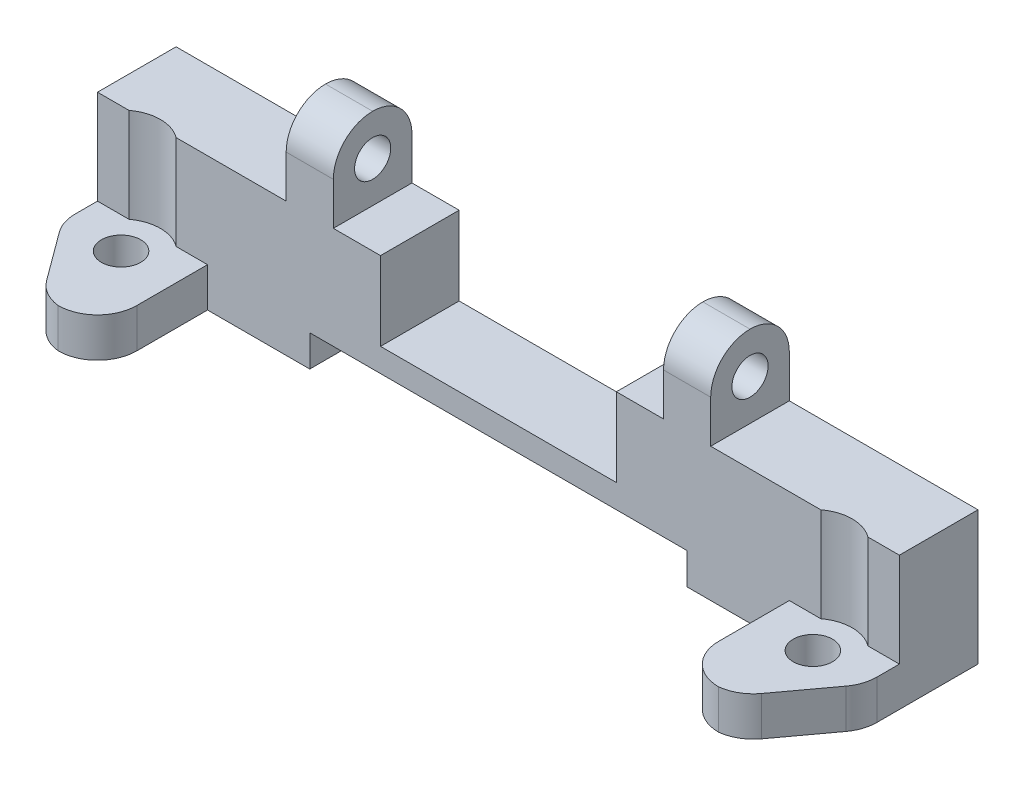
SolidWorks part; units mm, degrees
material "Sculpteo SLS"
ref_plane "Front Plane" through (0, 0, 0) normal (0, 0, 1) x (1, 0, 0)
ref_plane "Top Plane" through (0, 0, 0) normal (0, 1, 0) x (1, 0, 0)
ref_plane "Right Plane" through (0, 0, 0) normal (1, 0, 0) x (0, 0, -1)
sketch "Sketch1" plane through (0, 0, 0) normal (0, 1, 0) x (1, 0, 0)
  line L1 (25.5, -2.5) -> (-25.5, -2.5)
  line L2 (25.5, -2.5) -> (25.5, 2.5)
  line L3 (25.5, 2.5) -> (-25.5, 2.5)
  line L4 (-25.5, -2.5) -> (-25.5, 2.5)
  line L5 (25.5, -2.5) -> (-25.5, 2.5) construction
  line L6 (25.5, 2.5) -> (-25.5, -2.5) construction
  point P0 (0, 0)
  dimension "D1" = 51
  dimension "D2" = 5
extrude "Boss-Extrude1" add sketch "Sketch1" along normal blind 8.5
sketch "Sketch2" plane through (0, 8.5, 0) normal (0, 1, 0) x (1, 0, 0)
  line L0 (25.5, 2.5) -> (-25.5, 2.5) construction
  line L1 (7.5, -2.5) -> (-7.5, -2.5)
  line L2 (7.5, -2.5) -> (7.5, 2.5)
  line L3 (7.5, 2.5) -> (-7.5, 2.5)
  line L4 (-7.5, -2.5) -> (-7.5, 2.5)
  line L5 (7.5, -2.5) -> (-7.5, 2.5) construction
  line L6 (7.5, 2.5) -> (-7.5, -2.5) construction
  point P0 (0, 0)
  dimension "D1" = 15
extrude "Cut-Extrude1" cut sketch "Sketch2" against normal blind 5
sketch "Sketch3" plane through (0, 0, 0) normal (0, -1, 0) x (1, 0, 0)
  line L0 (-25.5, 2.5) -> (25.5, 2.5) construction
  line L1 (12, -2.5) -> (-12, -2.5)
  line L2 (12, -2.5) -> (12, 2.5)
  line L3 (12, 2.5) -> (-12, 2.5)
  line L4 (-12, -2.5) -> (-12, 2.5)
  line L5 (12, -2.5) -> (-12, 2.5) construction
  line L6 (12, 2.5) -> (-12, -2.5) construction
  point P0 (0, 0)
  dimension "D1" = 24
extrude "Cut-Extrude2" cut sketch "Sketch3" against normal blind 2
sketch "Sketch4" plane through (0, 0, 2.5) normal (0, 0, 1) x (1, 0, 0)
  line L0 (-25.5, 8.5) -> (-25.5, 0) construction
  line L1 (-25.5, 2.5) -> (-18.5, 2.5)
  line L2 (-25.5, 2.5) -> (-25.5, 0)
  line L3 (-25.5, 0) -> (-18.5, 0)
  line L4 (-18.5, 2.5) -> (-18.5, 0)
  line L5 (-25.5, 0) -> (-12, 0) construction
  line L6 (0, 0) -> (0, -50000) construction
  line L7 (18.5, 2.5) -> (18.5, 0)
  line L8 (25.5, 0) -> (18.5, 0)
  line L9 (25.5, 2.5) -> (25.5, 0)
  line L10 (25.5, 2.5) -> (18.5, 2.5)
  dimension "D1" = 7
  dimension "D2" = 2.5
extrude "Boss-Extrude2" add sketch "Sketch4" along normal blind 7
sketch "Sketch5" plane through (0, 8.5, 0) normal (0, 1, 0) x (1, 0, 0)
  line L0 (-7.5, 2.5) -> (-25.5, 2.5) construction
  line L1 (-10.5, 2.5) -> (-13.5, 2.5)
  line L2 (-10.5, 2.5) -> (-10.5, -2.5)
  line L3 (-10.5, -2.5) -> (-13.5, -2.5)
  line L4 (-13.5, 2.5) -> (-13.5, -2.5)
  line L5 (-25.5, -2.5) -> (-7.5, -2.5) construction
  line L6 (-7.5, 2.5) -> (-7.5, -2.5) construction
  line L7 (0, 0) -> (0, -50000) construction
  line L8 (13.5, 2.5) -> (13.5, -2.5)
  line L9 (10.5, -2.5) -> (13.5, -2.5)
  line L10 (10.5, 2.5) -> (10.5, -2.5)
  line L11 (10.5, 2.5) -> (13.5, 2.5)
  dimension "D1" = 3
  dimension "D2" = 3
extrude "Boss-Extrude3" add sketch "Sketch5" along normal blind 5.2
sketch "Sketch6" plane through (0, 2.5, 0) normal (0, 1, 0) x (1, 0, 0)
  line L2 (0, 0) -> (0, -50000) construction
  line L3 (-13.5, 2.5) -> (-25.5, 2.5) construction
  circle A0 centre (-22, -4.5) radius 1.25
  circle A1 centre (22, -4.5) radius 1.25
  dimension "D1" = 2.5
  dimension "D2" = 44
  dimension "D3" = 7
extrude "Cut-Extrude3" cut sketch "Sketch6" against normal through all
sketch "Sketch7" plane through (0, 2, 0) normal (0, -1, 0) x (1, 0, 0)
  line L0 (0, 0) -> (0, -50000) construction
  line L1 (12, 2.5) -> (-12, 2.5) construction
  circle A0 centre (-8.5, 0.5) radius 0.75
  circle A1 centre (8.5, 0.5) radius 0.75
  dimension "D3" = 1.5
  dimension "D1" = 17
  dimension "D2" = 2
extrude "Cut-Extrude4" cut sketch "Sketch7" against normal blind 5
sketch "Sketch8" plane through (-13.5, 0, 0) normal (-1, 0, 0) x (0, 0, 1)
  line L0 (-2.5, 13.7) -> (2.5, 13.7) construction
  line L1 (-2.5, 13.7) -> (-2.5, 8.5) construction
  circle A0 centre (0, 11.1) radius 1.15
  point P5 (0, 13.7)
  point P8 (-2.5, 11.1)
  dimension "D1" = 2.3
extrude "Cut-Extrude5" cut sketch "Sketch8" against normal through all
sketch "Sketch9" plane through (0, 8.5, 0) normal (0, 1, 0) x (1, 0, 0)
  circle A0 centre (-22, -4.5) radius 2.5
  circle A1 centre (22, -4.5) radius 2.5
  dimension "D1" = 5
extrude "Cut-Extrude6" cut sketch "Sketch9" against normal up to surface (6 mm away) up to face at (-22, 2.5, 5.75)
fillet "Fillet1" radius 2.5 8 edges at (12, 13.7, 2.5) (12, 13.7, -2.5) (-12, 13.7, -2.5) (-12, 13.7, 2.5) (25.5, 1.25, 9.5) (18.5, 1.25, 9.5) (-18.5, 1.25, 9.5) (-25.5, 1.25, 9.5)
sketch "Sketch10" plane through (0, 2.5, 0) normal (0, 1, 0) x (1, 0, 0)
  line L0 (-25.5, -4.75) -> (-22, -9.5)
  line L1 (-25.5, -7) -> (-25.5, -2.5) construction
  line L2 (-21, -9.5) -> (-23, -9.5) construction
  line L3 (-25.5, -4.75) -> (-25.5, -9.5)
  line L4 (-25.5, -9.5) -> (-22, -9.5)
  line L5 (25.5, -4.75) -> (25.5, -9.5)
  line L6 (25.5, -7) -> (25.5, -2.5) construction
  line L7 (25.5, -9.5) -> (22, -9.5)
  line L8 (23, -9.5) -> (21, -9.5) construction
  line L9 (22, -9.5) -> (25.5, -4.75)
extrude "Cut-Extrude7" cut sketch "Sketch10" against normal through all
fillet "Fillet2" radius 2.5 4 edges at (25.5, 1.25, 4.75) (22, 1.25, 9.5) (-22, 1.25, 9.5) (-25.5, 1.25, 4.75)
